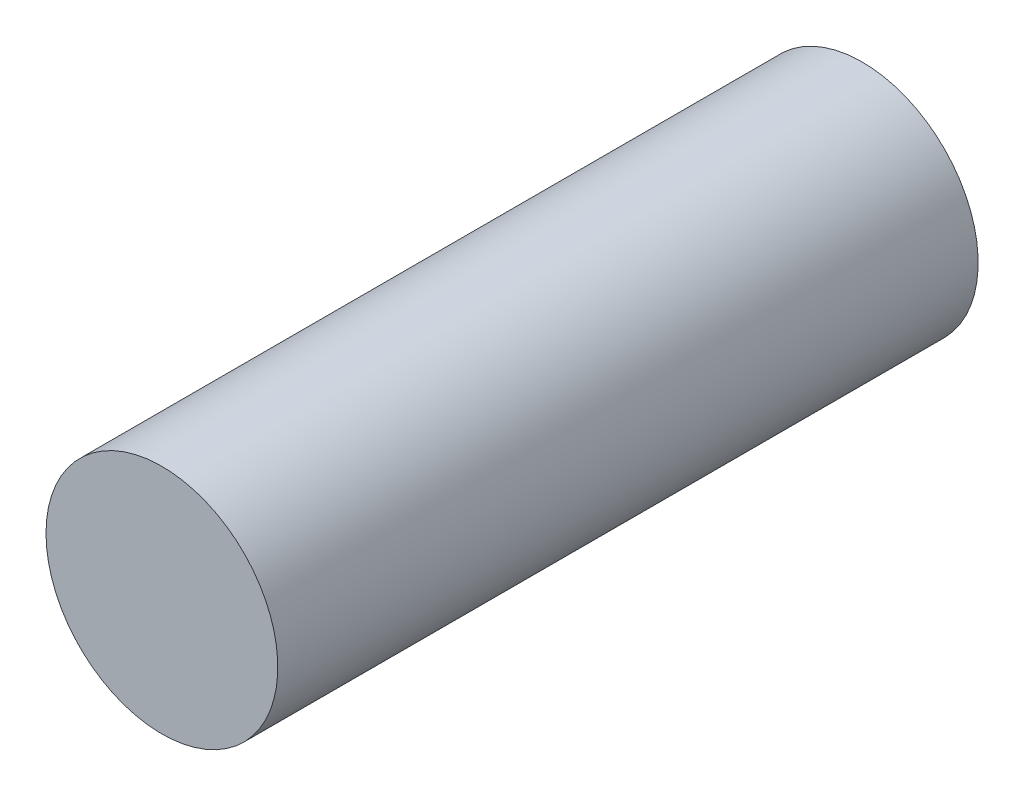
SolidWorks part; units mm, degrees
ref_plane "Front Plane" through (0, 0, 0) normal (1, 0, 0) x (0, 1, 0)
ref_plane "Top Plane" through (0, 0, 0) normal (0, 0, 1) x (0, 1, 0)
ref_plane "Right Plane" through (0, 0, 0) normal (0, 1, 0) x (-1, 0, 0)
sketch "Sketch1" plane through (0, 0, 0) normal (0, 0, 1) x (0, 1, 0)
  circle A0 centre (0, 0) radius 12.6111
  dimension "D1" = 25.2222
extrude "Boss-Extrude1" add sketch "Sketch1" along normal blind 76.2
